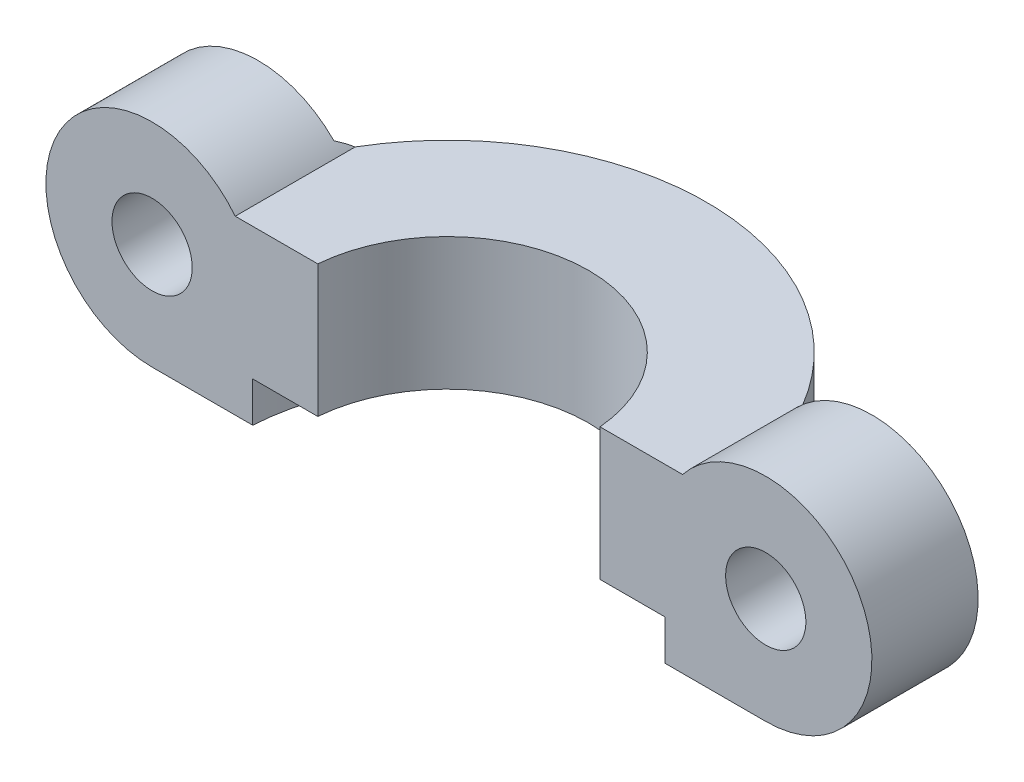
SolidWorks part; units mm, degrees
ref_plane "Front Plane" through (0, 0, 0) normal (0, 0, 1) x (1, 0, 0)
ref_plane "Top Plane" through (0, 0, 0) normal (0, 1, 0) x (1, 0, 0)
ref_plane "Right Plane" through (0, 0, 0) normal (1, 0, 0) x (0, 0, -1)
sketch "Sketch1" plane through (0, 0, 0) normal (0, 1, 0) x (1, 0, 0)
  line L5 (17.5, 12) -> (-17.5, 12)
  line L6 (17.5, 12) -> (17.5, 0)
  line L7 (17.5, 0) -> (-17.5, 0)
  line L8 (-17.5, 12) -> (-17.5, 0)
  line L9 (0, 0) -> (0, 12) construction
  line L10 (17.5, 6) -> (-17.5, 6) construction
  point P56 (0, 6)
  dimension "D1" = 35
  dimension "D2" = 12
extrude "Boss-Extrude1" add sketch "Sketch1" along normal mid plane 15
sketch "Sketch2" plane through (0, 0, 0) normal (0, 0, 1) x (1, 0, 0)
  line L0 (0, 7.5) -> (0, -7.5) construction
  line L1 (-17.5, 7.5) -> (17.5, 7.5) construction
  line L2 (-17.5, -7.5) -> (17.5, -7.5) construction
  line L3 (8.75, 7.5) -> (8.75, 2.8)
  line L4 (8.75, 2.8) -> (6, 2.8)
  line L5 (6, 2.8) -> (6, -2.8)
  line L6 (6, -2.8) -> (8.75, -2.8)
  line L7 (8.75, -2.8) -> (8.75, -7.5)
  line L8 (8.75, -7.5) -> (0, -7.5)
  line L9 (8.75, 7.5) -> (0, 7.5)
  line L10 (0, 7.5) -> (0, -7.5)
  dimension "D1" = 12
  dimension "D2" = 8.75
  dimension "D3" = 5.6
revolve "Cut-Revolve1" cut sketch "Sketch2" angle 360 about L0
sketch "Sketch3" plane through (0, 7.5, 0) normal (0, 1, 0) x (1, 0, 0)
  line L0 (17.5, 0) -> (17.5, 12) construction
  line L1 (-17.5, 0) -> (17.5, 0)
  line L2 (-17.5, 0) -> (-17.5, 0.5)
  line L3 (-17.5, 0.5) -> (17.5, 0.5)
  line L4 (17.5, 0) -> (17.5, 0.5)
  line L5 (0, 0.5) -> (0, 0) construction
  line L6 (-17.5, 0.25) -> (17.5, 0.25) construction
  point P72 (0, 0.25)
  dimension "D1" = 0.5
extrude "Cut-Extrude1" cut sketch "Sketch3" against normal through all
hole_wizard "M3 Clearance Hole1" positions "Sketch4" profile "Sketch5" hole size "M3" standard "ANSI Metric" end condition through all
sketch "Sketch4" plane through (0, 0, -12) normal (0, 0, -1) x (-1, 0, 0)
  line L0 (-13, 0) -> (13, 0) construction
  point P0 (13, 0)
  point P2 (-13, 0)
  dimension "D1" = 26
sketch "Sketch5" plane through (-13, 0, -12) normal (1, 0, 0) x (0, 1, 0)
  line L0 (0, 0) -> (0, 11.5)
  line L1 (0, 11.5) -> (1.7, 11.5)
  line L2 (1.7, 11.5) -> (1.7, 0)
  line L5 (1.7, 0) -> (0, 0)
  line L11 (0, -6.35) -> (0, 107.95) construction
  dimension "Thru Hole Dia." = 3.4
  dimension "Thru Hole Depth" = 11.5
sketch "Sketch6" plane through (0, 7.5, 0) normal (0, 1, 0) x (1, 0, 0)
  line L0 (-17.5, 12) -> (-17.5, 0.5) construction
  line L1 (17.5, 12) -> (-17.5, 12)
  line L2 (17.5, 12) -> (17.5, 5)
  line L3 (17.5, 5) -> (-17.5, 5)
  line L4 (-17.5, 12) -> (-17.5, 5)
  line L5 (0, 5) -> (0, 12) construction
  line L6 (17.5, 8.5) -> (-17.5, 8.5) construction
  circle A0 centre (0, 0) radius 11
  point P124 (0, 8.5)
  line M2 (-17.5, 12) -> (-17.5, 0.5)
  line M6 (17.5, 0.5) -> (17.5, 12)
  line M7 (17.5, 12) -> (-17.5, 12)
  dimension "D1" = 5
  dimension "D2" = 22
extrude "Cut-Extrude2" cut sketch "Sketch6" against normal through all contours A0 L3 M6 M7 M2 region at (17.1431, 7.5, -8.5)
sketch "Sketch7" plane through (0, 0, -0.5) normal (0, 0, 1) x (1, 0, 0)
  line L0 (-17.5, -7.5) -> (-17.5, 7.5) construction
  line L1 (-17.5, 2.8) -> (17.5, 2.8)
  line L2 (-17.5, 2.8) -> (-17.5, -2.8)
  line L3 (-17.5, -2.8) -> (17.5, -2.8)
  line L4 (17.5, 2.8) -> (17.5, -2.8)
  line L5 (0, -2.8) -> (0, 2.8) construction
  line L6 (-17.5, 0) -> (17.5, 0) construction
  line L7 (17.5, -7.5) -> (17.5, 7.5) construction
  line L8 (-13, -4.5) -> (13, -4.5)
  circle A0 centre (-13, 0) radius 4.5
  circle A1 centre (13, 0) radius 4.5
  circle A2 centre (13, 0) radius 1.7 construction
  point P184 (0, 0)
  circle M3 centre (13, 0) radius 1.7
  line M5 (8.7357, 2.8) -> (5.9791, 2.8)
  line M6 (5.9791, 2.8) -> (5.9791, -2.8)
  line M7 (5.9791, -2.8) -> (8.7357, -2.8)
  line M8 (8.7357, -2.8) -> (8.7357, -7.5)
  dimension "D1" = 5.6
extrude "Cut-Extrude3" cut sketch "Sketch7" against normal through all flip side to cut contours L1 A0 | L1 A0 L3 | A0 L3 L1 M6 | L3 A0 | A1 L1 L3 M5 M6 M7 | L1 A1 L3 M3 | L1 A1 | L3 A1 | A0 L8 L3 M8 M7 | A1 L3 L8 M8 region at (-1.4183, 0, -0.5) region at (7.4091, 0, -0.5) region at (-13, 0, -0.5) region at (-13, 3.4924, -0.5) region at (-0.9221, -3.6701, -0.5) region at (13, 3.4924, -0.5) region at (13, 2.694, -0.5) region at (9.8235, -3.8638, -0.5) region at (-13, -3.4924, -0.5) region at (13, -3.4924, -0.5)
